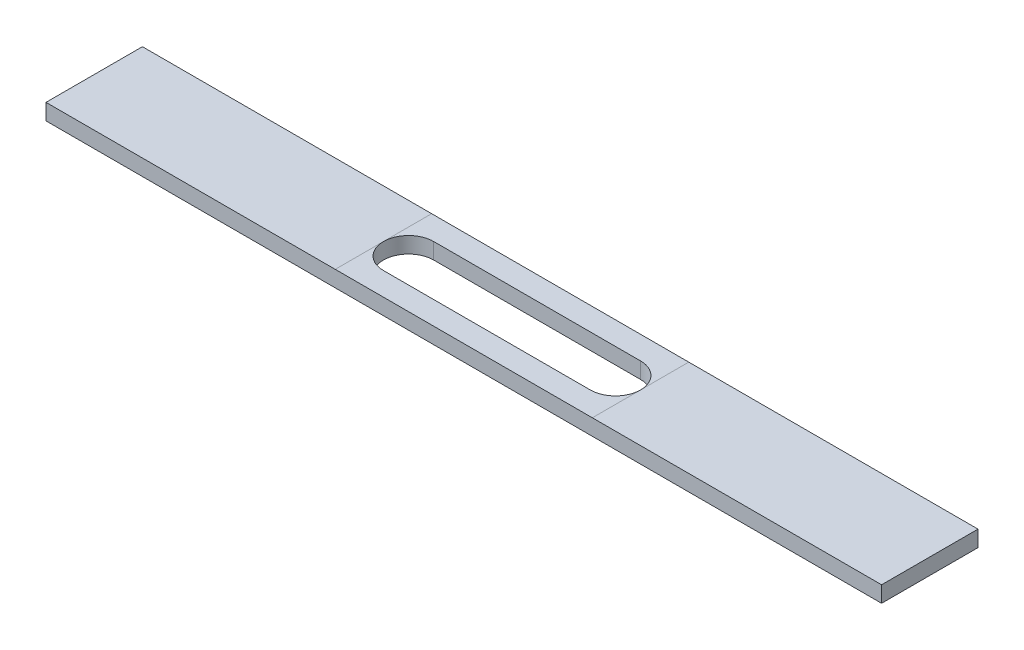
SolidWorks part; units mm, degrees
material "Acrylic (Medium-high impact)"
ref_plane "Front Plane" through (0, 0, 0) normal (0, 0, 1) x (1, 0, 0)
ref_plane "Top Plane" through (0, 0, 0) normal (0, 1, 0) x (1, 0, 0)
ref_plane "Right Plane" through (0, 0, 0) normal (1, 0, 0) x (0, 0, -1)
sketch "Sketch1" plane through (0, 0, 0) normal (0, 1, 0) x (1, 0, 0)
  line L1 (82.55, -9.525) -> (-82.55, -9.525)
  line L2 (82.55, -9.525) -> (82.55, 9.525)
  line L3 (82.55, 9.525) -> (-82.55, 9.525)
  line L4 (-82.55, -9.525) -> (-82.55, 9.525)
  line L5 (82.55, -9.525) -> (-82.55, 9.525) construction
  line L6 (82.55, 9.525) -> (-82.55, -9.525) construction
  point P0 (0, 0)
  dimension "D1" = 19.05
  dimension "D2" = 165.1
extrude "Boss-Extrude1" add sketch "Sketch1" along normal blind 3.175 contours L3 L4 L1 L2
sketch "Sketch3" plane through (0, 3.175, 0) normal (0, 1, 0) x (1, 0, 0)
  line L0 (-25.4, 9.525) -> (-25.4, -9.525)
  line L1 (82.55, 9.525) -> (-82.55, 9.525) construction
  line L2 (82.55, -9.525) -> (-82.55, -9.525) construction
  line L3 (25.4, 9.525) -> (25.4, -9.525)
  line L4 (25.4, 0) -> (-25.4, 0) construction
  point P12 (0, 0)
  dimension "D1" = 50.8
split line "Split Line1"
sketch "Sketch4" plane through (0, 3.175, 0) normal (0, 1, 0) x (1, 0, 0)
  line L0 (-25.4, -9.525) -> (-25.4, 9.525) construction
  ellipse E0 centre (0, 0) end of major axis (-25.4, 0) minor radius 6.0325
  dimension "D1" = 12.065
extrude "Ellipse" [suppressed] cut sketch "Sketch4" against normal through all
sketch "Sketch5" plane through (0, 3.175, 0) normal (0, 1, 0) x (1, 0, 0)
  line L0 (-20.4343, 0) -> (20.4343, 0) construction
  line L4 (-20.4343, 4.9657) -> (20.4343, 4.9657)
  line L5 (-20.4343, -4.9657) -> (20.4343, -4.9657)
  line L6 (25.4, -9.525) -> (25.4, 9.525) construction
  arc A2 (-20.4343, 4.9657) -> (-20.4343, -4.9657) centre (-20.4343, 0) ccw
  arc A3 (20.4343, -4.9657) -> (20.4343, 4.9657) centre (20.4343, 0) ccw
  point P2 (0, 0)
  dimension "D1" = 9.9314
extrude "Slot" cut sketch "Sketch5" against normal through all
sketch "Sketch6" [suppressed] plane through (0, 3.175, 0) normal (0, 1, 0) x (1, 0, 0)
  line L0 (-24.2316, 7.1289) -> (-19.1516, 7.1289) construction
  line L1 (-24.2316, 8.2973) -> (-19.1516, 8.2973)
  line L2 (-24.2316, 5.9605) -> (-19.1516, 5.9605)
  line L3 (-15.555, 7.1289) -> (-10.475, 7.1289) construction
  line L4 (-15.555, 8.2973) -> (-10.475, 8.2973)
  line L5 (-15.555, 5.9605) -> (-10.475, 5.9605)
  line L6 (-6.8783, 7.1289) -> (-1.7983, 7.1289) construction
  line L7 (-6.8783, 8.2973) -> (-1.7983, 8.2973)
  line L8 (-6.8783, 5.9605) -> (-1.7983, 5.9605)
  line L9 (1.7983, 7.1289) -> (6.8783, 7.1289) construction
  line L10 (1.7983, 8.2973) -> (6.8783, 8.2973)
  line L11 (1.7983, 5.9605) -> (6.8783, 5.9605)
  line L12 (10.475, 7.1289) -> (15.555, 7.1289) construction
  line L13 (10.475, 8.2973) -> (15.555, 8.2973)
  line L14 (10.475, 5.9605) -> (15.555, 5.9605)
  line L15 (19.1516, 7.1289) -> (24.2316, 7.1289) construction
  line L16 (19.1516, 8.2973) -> (24.2316, 8.2973)
  line L17 (19.1516, 5.9605) -> (24.2316, 5.9605)
  line L18 (-15.555, 3.5645) -> (-10.475, 3.5645) construction
  line L19 (-15.555, 4.7329) -> (-10.475, 4.7329)
  line L20 (-15.555, 2.3961) -> (-10.475, 2.3961)
  line L21 (-6.8783, 3.5645) -> (-1.7983, 3.5645) construction
  line L22 (-6.8783, 4.7329) -> (-1.7983, 4.7329)
  line L23 (-6.8783, 2.3961) -> (-1.7983, 2.3961)
  line L24 (1.7983, 3.5645) -> (6.8783, 3.5645) construction
  line L25 (1.7983, 4.7329) -> (6.8783, 4.7329)
  line L26 (1.7983, 2.3961) -> (6.8783, 2.3961)
  line L27 (10.475, 3.5645) -> (15.555, 3.5645) construction
  line L28 (10.475, 4.7329) -> (15.555, 4.7329)
  line L29 (10.475, 2.3961) -> (15.555, 2.3961)
  line L30 (19.1516, 3.5645) -> (24.2316, 3.5645) construction
  line L31 (19.1516, 4.7329) -> (24.2316, 4.7329)
  line L32 (19.1516, 2.3961) -> (24.2316, 2.3961)
  line L33 (-15.555, 0) -> (-10.475, 0) construction
  line L34 (-15.555, 1.1684) -> (-10.475, 1.1684)
  line L35 (-15.555, -1.1684) -> (-10.475, -1.1684)
  line L36 (-6.8783, 0) -> (-1.7983, 0) construction
  line L37 (-6.8783, 1.1684) -> (-1.7983, 1.1684)
  line L38 (-6.8783, -1.1684) -> (-1.7983, -1.1684)
  line L39 (1.7983, 0) -> (6.8783, 0) construction
  line L40 (1.7983, 1.1684) -> (6.8783, 1.1684)
  line L41 (1.7983, -1.1684) -> (6.8783, -1.1684)
  line L42 (10.475, 0) -> (15.555, 0) construction
  line L43 (10.475, 1.1684) -> (15.555, 1.1684)
  line L44 (10.475, -1.1684) -> (15.555, -1.1684)
  line L45 (19.1516, 0) -> (24.2316, 0) construction
  line L46 (19.1516, 1.1684) -> (24.2316, 1.1684)
  line L47 (19.1516, -1.1684) -> (24.2316, -1.1684)
  line L48 (-15.555, -3.5645) -> (-10.475, -3.5645) construction
  line L49 (-15.555, -2.3961) -> (-10.475, -2.3961)
  line L50 (-15.555, -4.7329) -> (-10.475, -4.7329)
  line L51 (-6.8783, -3.5645) -> (-1.7983, -3.5645) construction
  line L52 (-6.8783, -2.3961) -> (-1.7983, -2.3961)
  line L53 (-6.8783, -4.7329) -> (-1.7983, -4.7329)
  line L54 (1.7983, -3.5645) -> (6.8783, -3.5645) construction
  line L55 (1.7983, -2.3961) -> (6.8783, -2.3961)
  line L56 (1.7983, -4.7329) -> (6.8783, -4.7329)
  line L57 (10.475, -3.5645) -> (15.555, -3.5645) construction
  line L58 (10.475, -2.3961) -> (15.555, -2.3961)
  line L59 (10.475, -4.7329) -> (15.555, -4.7329)
  line L60 (19.1516, -3.5645) -> (24.2316, -3.5645) construction
  line L61 (19.1516, -2.3961) -> (24.2316, -2.3961)
  line L62 (19.1516, -4.7329) -> (24.2316, -4.7329)
  line L63 (-15.555, -7.1289) -> (-10.475, -7.1289) construction
  line L64 (-15.555, -5.9605) -> (-10.475, -5.9605)
  line L65 (-15.555, -8.2973) -> (-10.475, -8.2973)
  line L66 (-6.8783, -7.1289) -> (-1.7983, -7.1289) construction
  line L67 (-6.8783, -5.9605) -> (-1.7983, -5.9605)
  line L68 (-6.8783, -8.2973) -> (-1.7983, -8.2973)
  line L69 (1.7983, -7.1289) -> (6.8783, -7.1289) construction
  line L70 (1.7983, -5.9605) -> (6.8783, -5.9605)
  line L71 (1.7983, -8.2973) -> (6.8783, -8.2973)
  line L72 (10.475, -7.1289) -> (15.555, -7.1289) construction
  line L73 (10.475, -5.9605) -> (15.555, -5.9605)
  line L74 (10.475, -8.2973) -> (15.555, -8.2973)
  line L75 (19.1516, -7.1289) -> (24.2316, -7.1289) construction
  line L76 (19.1516, -5.9605) -> (24.2316, -5.9605)
  line L77 (19.1516, -8.2973) -> (24.2316, -8.2973)
  line L78 (-24.2316, 3.5645) -> (-19.1516, 3.5645) construction
  line L79 (-24.2316, 4.7329) -> (-19.1516, 4.7329)
  line L80 (-24.2316, 2.3961) -> (-19.1516, 2.3961)
  line L81 (-24.2316, 0) -> (-19.1516, 0) construction
  line L82 (-24.2316, 1.1684) -> (-19.1516, 1.1684)
  line L83 (-24.2316, -1.1684) -> (-19.1516, -1.1684)
  line L84 (-24.2316, -3.5645) -> (-19.1516, -3.5645) construction
  line L85 (-24.2316, -2.3961) -> (-19.1516, -2.3961)
  line L86 (-24.2316, -4.7329) -> (-19.1516, -4.7329)
  line L87 (-24.2316, -7.1289) -> (-19.1516, -7.1289) construction
  line L88 (-24.2316, -5.9605) -> (-19.1516, -5.9605)
  line L89 (-24.2316, -8.2973) -> (-19.1516, -8.2973)
  line L90 (-25.4, -9.525) -> (-25.4, 9.525) construction
  line L92 (25.4, -9.525) -> (25.4, 9.525) construction
  line L93 (-24.2316, 8.2973) -> (-24.2316, 9.525) construction
  line L94 (25.4, 9.525) -> (-25.4, 9.525) construction
  line L95 (-24.2316, -8.2973) -> (-24.2316, -9.525) construction
  line L96 (25.4, -9.525) -> (-25.4, -9.525) construction
  line L97 (-24.2316, -5.9605) -> (-24.2316, -4.7329) construction
  arc A0 (-24.2316, 8.2973) -> (-24.2316, 5.9605) centre (-24.2316, 7.1289) ccw
  arc A1 (-19.1516, 5.9605) -> (-19.1516, 8.2973) centre (-19.1516, 7.1289) ccw
  arc A2 (-15.555, 8.2973) -> (-15.555, 5.9605) centre (-15.555, 7.1289) ccw
  arc A3 (-10.475, 5.9605) -> (-10.475, 8.2973) centre (-10.475, 7.1289) ccw
  arc A4 (-6.8783, 8.2973) -> (-6.8783, 5.9605) centre (-6.8783, 7.1289) ccw
  arc A5 (-1.7983, 5.9605) -> (-1.7983, 8.2973) centre (-1.7983, 7.1289) ccw
  arc A6 (1.7983, 8.2973) -> (1.7983, 5.9605) centre (1.7983, 7.1289) ccw
  arc A7 (6.8783, 5.9605) -> (6.8783, 8.2973) centre (6.8783, 7.1289) ccw
  arc A8 (10.475, 8.2973) -> (10.475, 5.9605) centre (10.475, 7.1289) ccw
  arc A9 (15.555, 5.9605) -> (15.555, 8.2973) centre (15.555, 7.1289) ccw
  arc A10 (19.1516, 8.2973) -> (19.1516, 5.9605) centre (19.1516, 7.1289) ccw
  arc A11 (24.2316, 5.9605) -> (24.2316, 8.2973) centre (24.2316, 7.1289) ccw
  arc A12 (-15.555, 4.7329) -> (-15.555, 2.3961) centre (-15.555, 3.5645) ccw
  arc A13 (-10.475, 2.3961) -> (-10.475, 4.7329) centre (-10.475, 3.5645) ccw
  arc A14 (-6.8783, 4.7329) -> (-6.8783, 2.3961) centre (-6.8783, 3.5645) ccw
  arc A15 (-1.7983, 2.3961) -> (-1.7983, 4.7329) centre (-1.7983, 3.5645) ccw
  arc A16 (1.7983, 4.7329) -> (1.7983, 2.3961) centre (1.7983, 3.5645) ccw
  arc A17 (6.8783, 2.3961) -> (6.8783, 4.7329) centre (6.8783, 3.5645) ccw
  arc A18 (10.475, 4.7329) -> (10.475, 2.3961) centre (10.475, 3.5645) ccw
  arc A19 (15.555, 2.3961) -> (15.555, 4.7329) centre (15.555, 3.5645) ccw
  arc A20 (19.1516, 4.7329) -> (19.1516, 2.3961) centre (19.1516, 3.5645) ccw
  arc A21 (24.2316, 2.3961) -> (24.2316, 4.7329) centre (24.2316, 3.5645) ccw
  arc A22 (-15.555, 1.1684) -> (-15.555, -1.1684) centre (-15.555, 0) ccw
  arc A23 (-10.475, -1.1684) -> (-10.475, 1.1684) centre (-10.475, 0) ccw
  arc A24 (-6.8783, 1.1684) -> (-6.8783, -1.1684) centre (-6.8783, 0) ccw
  arc A25 (-1.7983, -1.1684) -> (-1.7983, 1.1684) centre (-1.7983, 0) ccw
  arc A26 (1.7983, 1.1684) -> (1.7983, -1.1684) centre (1.7983, 0) ccw
  arc A27 (6.8783, -1.1684) -> (6.8783, 1.1684) centre (6.8783, 0) ccw
  arc A28 (10.475, 1.1684) -> (10.475, -1.1684) centre (10.475, 0) ccw
  arc A29 (15.555, -1.1684) -> (15.555, 1.1684) centre (15.555, 0) ccw
  arc A30 (19.1516, 1.1684) -> (19.1516, -1.1684) centre (19.1516, 0) ccw
  arc A31 (24.2316, -1.1684) -> (24.2316, 1.1684) centre (24.2316, 0) ccw
  arc A32 (-15.555, -2.3961) -> (-15.555, -4.7329) centre (-15.555, -3.5645) ccw
  arc A33 (-10.475, -4.7329) -> (-10.475, -2.3961) centre (-10.475, -3.5645) ccw
  arc A34 (-6.8783, -2.3961) -> (-6.8783, -4.7329) centre (-6.8783, -3.5645) ccw
  arc A35 (-1.7983, -4.7329) -> (-1.7983, -2.3961) centre (-1.7983, -3.5645) ccw
  arc A36 (1.7983, -2.3961) -> (1.7983, -4.7329) centre (1.7983, -3.5645) ccw
  arc A37 (6.8783, -4.7329) -> (6.8783, -2.3961) centre (6.8783, -3.5645) ccw
  arc A38 (10.475, -2.3961) -> (10.475, -4.7329) centre (10.475, -3.5645) ccw
  arc A39 (15.555, -4.7329) -> (15.555, -2.3961) centre (15.555, -3.5645) ccw
  arc A40 (19.1516, -2.3961) -> (19.1516, -4.7329) centre (19.1516, -3.5645) ccw
  arc A41 (24.2316, -4.7329) -> (24.2316, -2.3961) centre (24.2316, -3.5645) ccw
  arc A42 (-15.555, -5.9605) -> (-15.555, -8.2973) centre (-15.555, -7.1289) ccw
  arc A43 (-10.475, -8.2973) -> (-10.475, -5.9605) centre (-10.475, -7.1289) ccw
  arc A44 (-6.8783, -5.9605) -> (-6.8783, -8.2973) centre (-6.8783, -7.1289) ccw
  arc A45 (-1.7983, -8.2973) -> (-1.7983, -5.9605) centre (-1.7983, -7.1289) ccw
  arc A46 (1.7983, -5.9605) -> (1.7983, -8.2973) centre (1.7983, -7.1289) ccw
  arc A47 (6.8783, -8.2973) -> (6.8783, -5.9605) centre (6.8783, -7.1289) ccw
  arc A48 (10.475, -5.9605) -> (10.475, -8.2973) centre (10.475, -7.1289) ccw
  arc A49 (15.555, -8.2973) -> (15.555, -5.9605) centre (15.555, -7.1289) ccw
  arc A50 (19.1516, -5.9605) -> (19.1516, -8.2973) centre (19.1516, -7.1289) ccw
  arc A51 (24.2316, -8.2973) -> (24.2316, -5.9605) centre (24.2316, -7.1289) ccw
  arc A52 (-24.2316, 4.7329) -> (-24.2316, 2.3961) centre (-24.2316, 3.5645) ccw
  arc A53 (-19.1516, 2.3961) -> (-19.1516, 4.7329) centre (-19.1516, 3.5645) ccw
  arc A54 (-24.2316, 1.1684) -> (-24.2316, -1.1684) centre (-24.2316, 0) ccw
  arc A55 (-19.1516, -1.1684) -> (-19.1516, 1.1684) centre (-19.1516, 0) ccw
  arc A56 (-24.2316, -2.3961) -> (-24.2316, -4.7329) centre (-24.2316, -3.5645) ccw
  arc A57 (-19.1516, -4.7329) -> (-19.1516, -2.3961) centre (-19.1516, -3.5645) ccw
  arc A58 (-24.2316, -5.9605) -> (-24.2316, -8.2973) centre (-24.2316, -7.1289) ccw
  arc A59 (-19.1516, -8.2973) -> (-19.1516, -5.9605) centre (-19.1516, -7.1289) ccw
  point P2 (-21.6916, 7.1289)
  point P11 (-13.015, 7.1289)
  point P18 (-4.3383, 7.1289)
  point P25 (4.3383, 7.1289)
  point P32 (13.015, 7.1289)
  point P39 (21.6916, 7.1289)
  point P46 (-13.015, 3.5645)
  point P53 (-4.3383, 3.5645)
  point P60 (4.3383, 3.5645)
  point P67 (13.015, 3.5645)
  point P74 (21.6916, 3.5645)
  point P81 (-13.015, 0)
  point P88 (-4.3383, 0)
  point P95 (4.3383, 0)
  point P102 (13.015, 0)
  point P109 (21.6916, 0)
  point P116 (-13.015, -3.5645)
  point P123 (-4.3383, -3.5645)
  point P130 (4.3383, -3.5645)
  point P137 (13.015, -3.5645)
  point P144 (21.6916, -3.5645)
  point P151 (-13.015, -7.1289)
  point P158 (-4.3383, -7.1289)
  point P165 (4.3383, -7.1289)
  point P172 (13.015, -7.1289)
  point P179 (21.6916, -7.1289)
  point P186 (-21.6916, 3.5645)
  point P193 (-21.6916, 0)
  point P200 (-21.6916, -3.5645)
  point P207 (-21.6916, -7.1289)
  point P217 (-25.4, 0)
  dimension "D4" = 1.1684
  dimension "D3" = 5.08
  dimension "D1" = 6
  dimension "D2" = 5
extrude "Slots" [suppressed] cut sketch "Sketch6" against normal through all
sketch "Sketch7" [suppressed] plane through (0, 3.175, 0) normal (0, 1, 0) x (1, 0, 0)
  line L1 (25.4, 9.525) -> (-25.4, 9.525) construction
  line L8 (7.366, 0) -> (0, 7.366)
  line L9 (7.366, 0) -> (0, -7.366)
  line L10 (0, 7.366) -> (-7.366, 0)
  line L11 (0, -7.366) -> (-7.366, 0)
  line L12 (7.366, 0) -> (-7.366, 0) construction
  line L13 (0, 7.366) -> (0, -7.366) construction
  line L14 (-10.668, 0) -> (-18.034, 7.366)
  line L15 (-10.668, 0) -> (-18.034, -7.366)
  line L16 (-18.034, 7.366) -> (-25.4, 0)
  line L17 (-18.034, -7.366) -> (-25.4, 0)
  line L18 (-10.668, 0) -> (-25.4, 0) construction
  line L19 (-18.034, 7.366) -> (-18.034, -7.366) construction
  line L20 (-25.4, -9.525) -> (-25.4, 9.525) construction
  line L21 (-14.9807, 7.366) -> (-9.017, 1.4023)
  line L22 (-25.4, 3.0533) -> (-25.4, 7.366)
  line L23 (-10.668, 0) -> (-7.366, 0) construction
  line L24 (-9.017, 1.4023) -> (-3.0533, 7.366)
  line L25 (-3.0533, 7.366) -> (-14.9807, 7.366)
  line L26 (-10.668, 0) -> (-9.017, 1.4023) construction
  line L27 (-7.366, 0) -> (-9.017, 1.4023) construction
  line L28 (-25.4, 3.0533) -> (-21.0873, 7.366)
  line L29 (-21.0873, 7.366) -> (-25.4, 7.366)
  line L30 (-21.0873, 7.366) -> (-18.034, 7.366) construction
  line L31 (-14.9807, 7.366) -> (-18.034, 7.366) construction
  line L32 (-3.0533, -7.366) -> (-14.9807, -7.366)
  line L33 (-9.017, -1.4023) -> (-3.0533, -7.366)
  line L34 (-14.9807, -7.366) -> (-9.017, -1.4023)
  line L35 (-25.4, -3.0533) -> (-25.4, -7.366)
  line L36 (-21.0873, -7.366) -> (-25.4, -7.366)
  line L37 (-25.4, -3.0533) -> (-21.0873, -7.366)
  line L38 (14.9807, 7.366) -> (18.034, 7.366) construction
  line L39 (21.0873, 7.366) -> (18.034, 7.366) construction
  line L40 (7.366, 0) -> (9.017, 1.4023) construction
  line L41 (10.668, 0) -> (9.017, 1.4023) construction
  line L42 (10.668, 0) -> (7.366, 0) construction
  line L43 (18.034, 7.366) -> (18.034, -7.366) construction
  line L44 (10.668, 0) -> (25.4, 0) construction
  line L45 (25.4, -3.0533) -> (21.0873, -7.366)
  line L46 (21.0873, -7.366) -> (25.4, -7.366)
  line L47 (25.4, -3.0533) -> (25.4, -7.366)
  line L48 (14.9807, -7.366) -> (9.017, -1.4023)
  line L49 (9.017, -1.4023) -> (3.0533, -7.366)
  line L50 (3.0533, -7.366) -> (14.9807, -7.366)
  line L51 (21.0873, 7.366) -> (25.4, 7.366)
  line L52 (25.4, 3.0533) -> (21.0873, 7.366)
  line L53 (3.0533, 7.366) -> (14.9807, 7.366)
  line L54 (9.017, 1.4023) -> (3.0533, 7.366)
  line L55 (25.4, 3.0533) -> (25.4, 7.366)
  line L56 (14.9807, 7.366) -> (9.017, 1.4023)
  line L57 (18.034, -7.366) -> (25.4, 0)
  line L58 (18.034, 7.366) -> (25.4, 0)
  line L59 (10.668, 0) -> (18.034, -7.366)
  line L60 (10.668, 0) -> (18.034, 7.366)
  point P1 (-18.034, 0)
  point P8 (0, 0)
  point P43 (18.034, 0)
  dimension "D1" = 2.159
  dimension "D2" = 2.159
extrude "Hash" [suppressed] cut sketch "Sketch7" against normal through all
fillet "Fillet2" [suppressed] radius 1.016
sketch "Sketch8" [suppressed] plane through (0, 3.175, 0) normal (0, 1, 0) x (1, 0, 0)
  line L0 (25.4, 0) -> (-25.4, 0) construction
  line L1 (25.4, -4.826) -> (-25.4, -4.826)
  line L2 (25.4, -4.826) -> (25.4, 4.826)
  line L3 (25.4, 4.826) -> (-25.4, 4.826)
  line L4 (-25.4, -4.826) -> (-25.4, 4.826)
  line L5 (25.4, -4.826) -> (-25.4, 4.826) construction
  line L6 (25.4, 4.826) -> (-25.4, -4.826) construction
  line L7 (-25.4, -9.525) -> (-25.4, 9.525) construction
  point P0 (0, 0)
  dimension "D1" = 9.652
extrude "Rectangle" [suppressed] cut sketch "Sketch8" against normal through all
fillet "Fillet3" [suppressed] radius 2.54
equation "\"D2@Sketch7\"=\"D1@Sketch7\""
